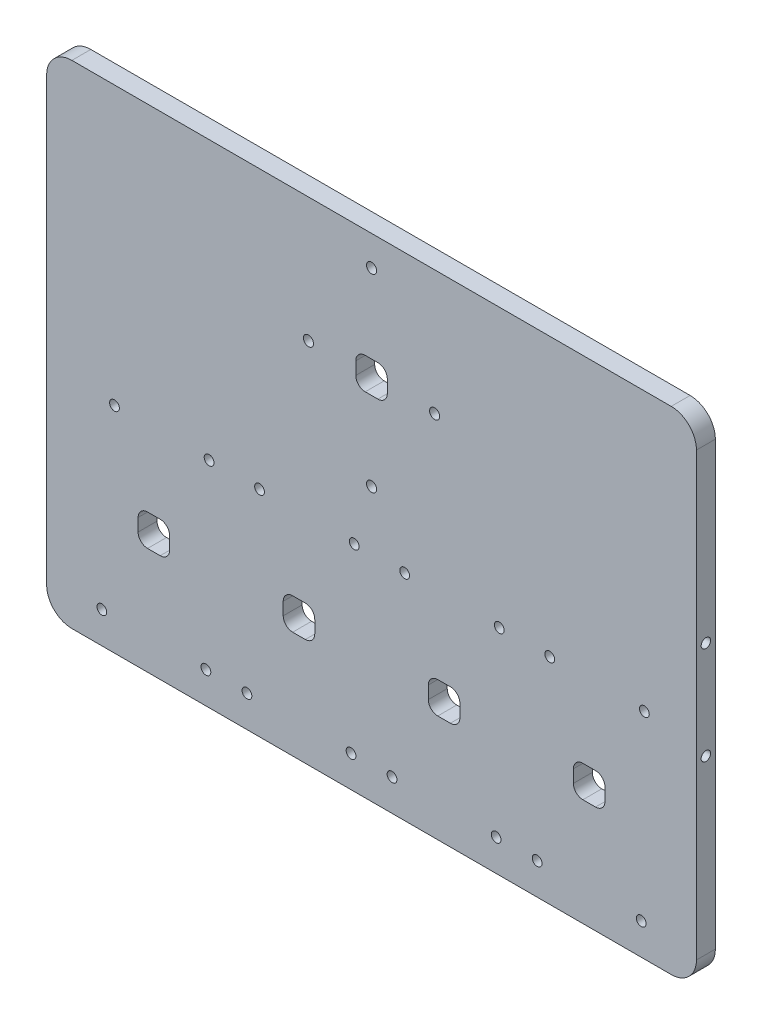
SolidWorks part; units mm, degrees
ref_plane "Front Plane" through (0, 0, 0) normal (1, 0, 0) x (0, 1, 0)
ref_plane "Top Plane" through (0, 0, 0) normal (0, 0, 1) x (0, 1, 0)
ref_plane "Right Plane" through (0, 0, 0) normal (0, 1, 0) x (-1, 0, 0)
sketch "Sketch1" plane through (0, 0, 0) normal (0, 0, 1) x (0, 1, 0)
  line L6 (0, 0) -> (31.4193, 0) construction
  line L7 (-70, -103) -> (70, -103)
  line L8 (-78, -95) -> (-78, 95)
  line L9 (-70, 103) -> (70, 103)
  line L10 (78, -95) -> (78, 95)
  line L11 (-78, -103) -> (78, 103) construction
  line L12 (-78, 103) -> (78, -103) construction
  line L13 (-68, -85.5) -> (-68, -52.5) construction
  line L15 (-10, -86.5) -> (-10, -56.5) construction
  line L23 (38.504, 27.5) -> (38.504, -27.5) construction
  line L25 (-78, 0) -> (-68, 0) construction
  line L30 (68, 0) -> (78, 0) construction
  line L34 (-73, -47.5) -> (-6, -47.5) construction
  line L35 (-73, -47.5) -> (-73, -90.5) construction
  line L40 (-73, -90.5) -> (-6, -90.5) construction
  line L41 (-6, -47.5) -> (-6, -90.5) construction
  line L42 (8.504, 20) -> (68.504, 20) construction
  line L43 (8.504, 20) -> (8.504, -20) construction
  line L44 (8.504, -20) -> (68.504, -20) construction
  line L45 (68.504, 20) -> (68.504, -20) construction
  line L46 (1.004, 27.5) -> (76.004, 27.5) construction
  line L47 (1.004, 27.5) -> (1.004, -27.5) construction
  line L48 (1.004, -27.5) -> (76.004, -27.5) construction
  line L49 (76.004, 27.5) -> (76.004, -27.5) construction
  arc A4 (70, -103) -> (78, -95) centre (70, -95) ccw
  arc A5 (-70, -103) -> (-78, -95) centre (-70, -95) cw
  arc A6 (-78, 95) -> (-70, 103) centre (-70, 95) cw
  arc A7 (70, 103) -> (78, 95) centre (70, 95) cw
  circle A8 centre (-68, -52.5) radius 1.55
  circle A9 centre (-68, -85.5) radius 1.55
  circle A10 centre (-10, -86.5) radius 1.55
  circle A11 centre (-10, -56.5) radius 1.55
  circle A24 centre (-68, -6.5) radius 1.55
  circle A25 centre (-68, -39.5) radius 1.55
  circle A26 centre (-10, -40.5) radius 1.55
  circle A27 centre (-10, -10.5) radius 1.55
  circle A28 centre (-68, 39.5) radius 1.55
  circle A29 centre (-68, 6.5) radius 1.55
  circle A30 centre (-10, 5.5) radius 1.55
  circle A31 centre (-10, 35.5) radius 1.55
  circle A32 centre (-68, 85.5) radius 1.55
  circle A33 centre (-68, 52.5) radius 1.55
  circle A34 centre (-10, 51.5) radius 1.55
  circle A35 centre (-10, 81.5) radius 1.55
  circle A40 centre (8.504, 0) radius 1.6
  circle A41 centre (38.504, 20) radius 1.6
  circle A42 centre (68.504, 0) radius 1.6
  circle A43 centre (38.504, -20) radius 1.6
  point P0 (0, 0)
  point P5 (0, 0)
  point P79 (68, 0)
  point P80 (68.504, 0)
  point P81 (-68, 81)
  dimension "D6" = 8
  dimension "D8" = 3.1
  dimension "D19" = 3.2
  dimension "D1" = 156
  dimension "D3" = 206
  dimension "D7" = 33
  dimension "D10" = 30
  dimension "D5" = 10
  dimension "D4" = 43
  dimension "D11" = 67
  dimension "D12" = 5
  dimension "D13" = 5
  dimension "D9" = 4
  dimension "D15" = 4
  dimension "D16" = 13
  dimension "D17" = 40
  dimension "D18" = 60
  dimension "D21" = 55
  dimension "D22" = 75
  dimension "D20" = 1.996
  dimension "D14" = 4
extrude "Boss-Extrude1" add sketch "Sketch1" along normal blind 6
sketch "Sketch3" plane through (103, 0, 0) normal (1, 0, 0) x (0, 1, 0)
  line L0 (0, 6) -> (0, 0) construction
  line L1 (-70, 6) -> (70, 6) construction
  line L2 (-70, 0) -> (70, 0) construction
  line L3 (-70, 3) -> (70, 3) construction
  line L4 (70, 6) -> (70, 0) construction
  line L5 (-70, 6) -> (-70, 0) construction
  circle A1 centre (-15.5, 3) radius 1.5
  circle A2 centre (15.5, 3) radius 1.5
  point P2 (0, 0)
  dimension "D1" = 3
  dimension "D2" = 3
  dimension "D3" = 31
extrude "Cut-Extrude1" cut sketch "Sketch3" against normal blind 10
extrude "Cut-Extrude2" cut sketch "Sketch3<2>" along normal blind 10 from surface starting at face at (-103, 0, 3)
sketch "Sketch3<2>" plane through (103, 0, 0) normal (1, 0, 0) x (0, 1, 0) same geometry as "Sketch3"
sketch "Sketch4" plane through (0, 0, 6) normal (0, 0, 1) x (1, 0, 0)
  line L0 (-69, -10) -> (-69, -68) construction
  line L1 (-71, -34) -> (-67, -34)
  line L2 (-74, -37) -> (-74, -41)
  line L3 (-71, -44) -> (-67, -44)
  line L4 (-64, -37) -> (-64, -41)
  line L5 (-81.5, -10) -> (-51.5, -10) construction
  line L6 (-85.5, -68) -> (-52.5, -68) construction
  line L7 (-74, -39) -> (-69, -39) construction
  line L8 (-28, -37) -> (-28, -41)
  line L9 (-25, -34) -> (-21, -34)
  line L10 (-25, -44) -> (-21, -44)
  line L11 (-18, -37) -> (-18, -41)
  line L12 (18, -37) -> (18, -41)
  line L13 (21, -34) -> (25, -34)
  line L14 (21, -44) -> (25, -44)
  line L15 (28, -37) -> (28, -41)
  line L16 (64, -37) -> (64, -41)
  line L17 (67, -34) -> (71, -34)
  line L18 (67, -44) -> (71, -44)
  line L19 (74, -37) -> (74, -41)
  line L20 (69, -8.2965) -> (69, -68) construction
  line L21 (52.5, -68) -> (85.5, -68) construction
  line L22 (-20, 38.504) -> (20, 38.504) construction
  line L23 (-2, 43.504) -> (2, 43.504)
  line L24 (-5, 40.504) -> (-5, 36.504)
  line L25 (-2, 33.504) -> (2, 33.504)
  line L26 (5, 40.504) -> (5, 36.504)
  line L27 (0, 68.504) -> (0, 8.504) construction
  arc A0 (71, -44) -> (74, -41) centre (71, -41) ccw
  arc A1 (71, -34) -> (74, -37) centre (71, -37) cw
  arc A2 (64, -37) -> (67, -34) centre (67, -37) cw
  arc A3 (64, -41) -> (67, -44) centre (67, -41) ccw
  arc A4 (25, -34) -> (28, -37) centre (25, -37) cw
  arc A5 (25, -44) -> (28, -41) centre (25, -41) ccw
  arc A6 (18, -41) -> (21, -44) centre (21, -41) ccw
  arc A7 (18, -37) -> (21, -34) centre (21, -37) cw
  arc A8 (-21, -44) -> (-18, -41) centre (-21, -41) ccw
  arc A9 (-21, -34) -> (-18, -37) centre (-21, -37) cw
  arc A10 (-28, -37) -> (-25, -34) centre (-25, -37) cw
  arc A11 (-28, -41) -> (-25, -44) centre (-25, -41) ccw
  arc A12 (-67, -44) -> (-64, -41) centre (-67, -41) ccw
  arc A13 (-74, -41) -> (-71, -44) centre (-71, -41) ccw
  arc A14 (-67, -34) -> (-64, -37) centre (-67, -37) cw
  arc A15 (-71, -34) -> (-74, -37) centre (-71, -37) ccw
  arc A16 (-5, 36.504) -> (-2, 33.504) centre (-2, 36.504) ccw
  arc A17 (2, 33.504) -> (5, 36.504) centre (2, 36.504) ccw
  arc A18 (2, 43.504) -> (5, 40.504) centre (2, 40.504) cw
  arc A19 (-2, 43.504) -> (-5, 40.504) centre (-2, 40.504) ccw
  point P5 (-58.5, -8.5)
  point P11 (-58.5, -8.5)
  point P67 (-64, -44)
  point P72 (-64, -34)
  point P75 (-74, -34)
  point P84 (-1.6814, 39.3465)
  point P85 (-8.4122, 34.3826)
  point P90 (0, 0)
  point P91 (0, 0)
  point P92 (0, 0)
  point P98 (5, 33.504)
  point P101 (5, 43.504)
  point P104 (-5, 43.504)
  dimension "D4" = 3
  dimension "D7" = 3
  dimension "D1" = 10
  dimension "D2" = 10
  dimension "D3" = 4
  dimension "D5" = 10
  dimension "D6" = 10
extrude "Cut-Extrude3" cut sketch "Sketch4" against normal up to next
equation "\"MotorDriverLength\"= 60mm"
equation "\"MotorLength\"= 60"
equation "\"MotorDriverWidth\"=44"
equation "\"MotorWidth\"= 37"
equation "\"InnerWallThickness\"=3"
equation "\"BatteryWidth\"= 60"
equation "\"OuterWallThickness\" = 8"
equation "\"CompartmentHeight\"=37"
equation "\"CompartmentWidth\"= \"MotorDriverLength\""
equation "\"MotorDiameter\"=37"
equation "\"BatteryHeight\"=24.2019"
equation "\"MotorDriverHeight\"=28"
equation "\"CircuitHeight\"=30"
equation "\"FanThickness\"= 10"
equation "\"FanHeight\"=50"
equation "\"MotorShaftHole\"=12"
equation "\"BearingBore\"=4"
equation "\"MinShinWidth\"= 20"
equation "\"ShinThickness\"=10"
equation "\"PivotDistance\"=30"
equation "\"ThighLength\"= 200"
equation "\"KneeLength\" =20"
equation "\"HipBore\"=27"
equation "\"ThighThickness\"=20"
equation "\"MaxBending\"=135"
equation "\"MaxStretchingAngle\"= 140"
equation "\"ThighJointDistance\"=157.485"
equation "\"ShinLength\"=120"
equation "\"BearingDiameter\"= 10"
equation "\"CircuitLength\"=50"
equation "\"ChessisInnerWidth\"= \"OuterWallThickness\" * 2 + \"MotorDriverLength\" + \"MotorDiameter\" + \"InnerWallThickness\" * 3 + \"CircuitLength\""
equation "\"ChessisHeight\"= \"BatteryHeight\" + 10 + \"InnerWallThickness\" + \"MotorDriverHeight\"*2 + 10 + \"OuterWallThickness\" * 2"
equation "\"ChassisWidth\"= \"MotorDriverWidth\"*4+30"
equation "\"D3@Sketch1\"=\"ChassisWidth\""
equation "\"D1@Sketch1\"=\"ChessisInnerWidth\"-\"OuterWallThickness\"*2"
